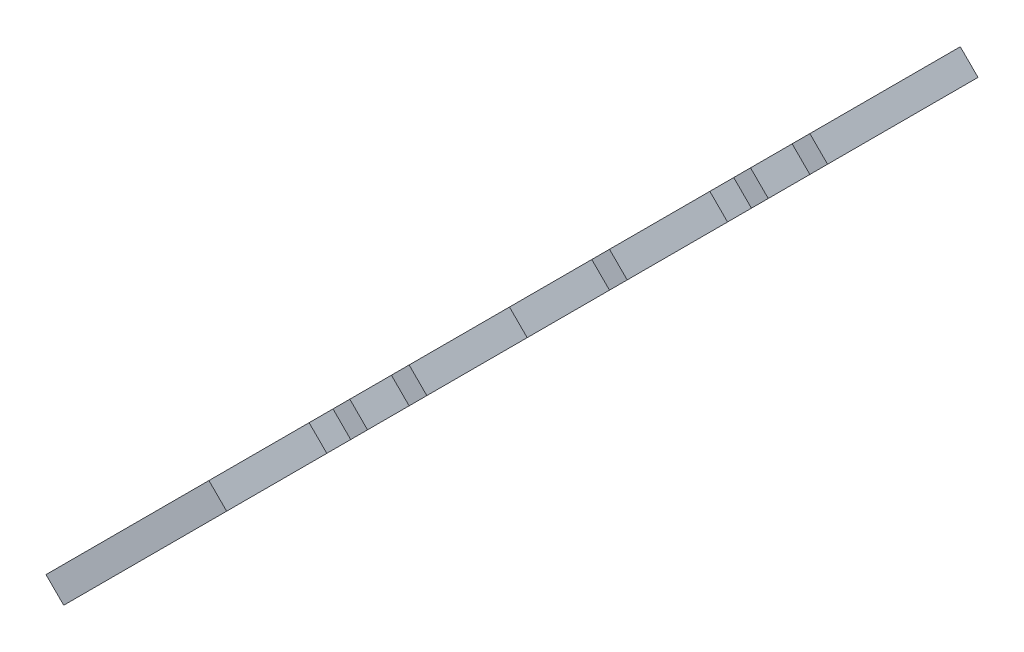
SolidWorks part; units mm, degrees
ref_plane "Front Plane" through (0, 0, 0) normal (0, 0, 1) x (1, 0, 0)
ref_plane "Top Plane" through (0, 0, 0) normal (0, 1, 0) x (1, 0, 0)
ref_plane "Right Plane" through (0, 0, 0) normal (1, 0, 0) x (0, 0, -1)
sketch "Sketch1" plane through (0, 0, 0) normal (0, 0, 1) x (1, 0, 0)
  line L0 (-110.4572, 6.7859) -> (-69.148, 48.095)
  line L1 (-110.4572, 6.7859) -> (-114.9473, 11.276)
  line L2 (-69.148, 48.095) -> (-73.6381, 52.5852)
  line L3 (-114.9473, 11.276) -> (-73.6381, 52.5852)
  line L4 (-74.5361, -29.1352) -> (-70.046, -24.645) construction
extrude "Boss-Extrude1" add sketch "Sketch1" along normal up to surface (190.5 mm away)
sketch "Sketch2" plane through (-63.1116, 63.1116, 0) normal (-0.7071, 0.7071, 0) x (0, 0, 1)
  line L0 (190.5, -14.8867) -> (0, -14.8867) construction
  line L1 (165.1, -21.2367) -> (139.7412, -21.2367)
  line L2 (165.1, -21.2367) -> (165.1, -14.8867)
  line L3 (165.1, -14.8867) -> (139.7412, -14.8867)
  line L4 (139.7412, -21.2367) -> (139.7412, -14.8867)
  line L5 (190.5, -73.3067) -> (0, -73.3067) construction
  line L6 (165.1, -66.9567) -> (139.7412, -66.9567)
  line L7 (165.1, -66.9567) -> (165.1, -73.3067)
  line L8 (165.1, -73.3067) -> (139.7412, -73.3067)
  line L9 (139.7412, -66.9567) -> (139.7412, -73.3067)
  dimension "D1" = 25.3588
extrude "Cut-Extrude1" cut sketch "Sketch2" against normal blind 6.35
pattern_linear "LPattern1" count 3 spacing 50.8 along (0, 0, -1) of "Cut-Extrude1"
sketch "Sketch3" plane through (0, 0, 0) normal (0, 0, -1) x (-1, 0, 0)
  line L0 (94.2927, 22.9503) -> (98.7828, 27.4404)
  line L1 (110.4572, 6.7859) -> (69.148, 48.095) construction
  line L2 (73.6381, 52.5852) -> (114.9473, 11.276) construction
  line L3 (98.7828, 27.4404) -> (89.8026, 36.4207)
  line L4 (89.8026, 36.4207) -> (85.3124, 31.9306)
  line L6 (85.3124, 31.9306) -> (94.2927, 22.9503)
  line L7 (98.7828, 36.4207) -> (83.4753, 21.1131) construction
  line L8 (69.148, 48.095) -> (73.6381, 52.5852) construction
  line L9 (114.9473, 11.276) -> (110.4572, 6.7859) construction
  dimension "D1" = 12.7
  dimension "D2" = 6.35
extrude "Boss-Extrude2" add sketch "Sketch3" along normal blind 6.35
sketch "Sketch5" plane through (-58.6215, 58.6215, 0) normal (0.7071, -0.7071, 0) x (0, 0, -1)
  line L0 (-179.8955, -73.3067) -> (-175.7045, -66.9567) construction
  line L1 (-190.5, -73.3067) -> (-165.1, -73.3067) construction
  line L2 (-179.8955, -66.9567) -> (-179.8955, -73.3067) construction
  line L3 (-175.7045, -73.3067) -> (-179.8955, -66.9567) construction
  line L4 (-175.7045, -66.9567) -> (-175.7045, -73.3067) construction
  line L5 (-78.2955, -73.3067) -> (-74.1045, -66.9567) construction
  line L6 (-88.9412, -73.3067) -> (-63.5, -73.3067) construction
  line L7 (-78.2955, -66.9567) -> (-78.2955, -73.3067) construction
  line L8 (-74.1045, -73.3067) -> (-78.2955, -66.9567) construction
  line L9 (-74.1045, -66.9567) -> (-74.1045, -73.3067) construction
  line L10 (-17.9705, -73.3067) -> (-13.7795, -66.9567) construction
  line L11 (-38.1412, -73.3067) -> (0, -73.3067) construction
  line L12 (-17.9705, -66.9567) -> (-17.9705, -73.3067) construction
  line L13 (-13.7795, -73.3067) -> (-17.9705, -66.9567) construction
  line L14 (-13.7795, -66.9567) -> (-13.7795, -73.3067) construction
  circle A0 centre (-177.8, -70.1317) radius 2.0955
  circle A1 centre (-76.2, -70.1317) radius 2.0955
  circle A2 centre (-15.875, -70.1317) radius 2.0955
  dimension "D1" = 4.191
extrude "Cut-Extrude2" cut sketch "Sketch5" against normal through all
ref_plane "Midplane" through (-31.1811, -31.1811, 0) normal (-0.7071, -0.7071, 0) x (-0.7071, 0.7071, 0)
mirror "Mirror1" about plane through (-31.1811, -31.1811, 0) normal (-0.7071, -0.7071, 0) of "Cut-Extrude2"
sketch "Sketch6" plane through (-63.1116, 63.1116, 0) normal (-0.7071, 0.7071, 0) x (0, 0, 1)
  line L0 (152.4206, -3.6091) -> (152.4206, -40.9822) construction
  line L1 (139.7412, -14.8867) -> (139.7412, -21.2367) construction
  line L2 (165.1, -21.2367) -> (165.1, -14.8867) construction
  line L3 (50.8206, 6.6062) -> (50.8206, -35.0025) construction
  line L4 (38.1412, -14.8867) -> (38.1412, -21.2367) construction
  line L5 (63.5, -21.2367) -> (63.5, -14.8867) construction
  line L7 (38.1412, -21.2367) -> (63.5, -21.2367) construction
  line L11 (139.7412, -21.2367) -> (165.1, -21.2367) construction
  line B0 (52.9542, -21.2367) -> (48.687, -21.2367)
  line B1 (48.687, -33.1747) -> (46.3756, -33.1747)
  line B2 (46.3756, -33.1747) -> (46.3756, -29.9997)
  line B3 (46.3756, -29.9997) -> (48.687, -29.9997)
  line B4 (48.687, -29.9997) -> (48.687, -21.2367)
  line B5 (48.687, -33.1747) -> (48.687, -36.4767)
  line B6 (48.687, -36.4767) -> (52.9542, -36.4767)
  line B7 (52.9542, -33.1747) -> (52.9542, -36.4767)
  line B8 (52.9542, -29.9997) -> (52.9542, -21.2367)
  line B9 (55.2656, -29.9997) -> (52.9542, -29.9997)
  line B10 (55.2656, -33.1747) -> (55.2656, -29.9997)
  line B11 (52.9542, -33.1747) -> (55.2656, -33.1747)
  line B12 (154.5542, -21.2367) -> (150.287, -21.2367)
  line B13 (150.287, -33.1747) -> (147.9756, -33.1747)
  line B14 (147.9756, -33.1747) -> (147.9756, -29.9997)
  line B15 (147.9756, -29.9997) -> (150.287, -29.9997)
  line B16 (150.287, -29.9997) -> (150.287, -21.2367)
  line B17 (150.287, -33.1747) -> (150.287, -36.4767)
  line B18 (150.287, -36.4767) -> (154.5542, -36.4767)
  line B19 (154.5542, -33.1747) -> (154.5542, -36.4767)
  line B20 (154.5542, -29.9997) -> (154.5542, -21.2367)
  line B21 (156.8656, -29.9997) -> (154.5542, -29.9997)
  line B22 (156.8656, -33.1747) -> (156.8656, -29.9997)
  line B23 (154.5542, -33.1747) -> (156.8656, -33.1747)
sketch_block_instance "TSlot-1"
sketch_block "TSlot" parameters "D1"=3.302, "D2"=3.175
sketch_block_instance "TSlot-2"
extrude "Cut-Extrude3" cut sketch "Sketch6" against normal through all
mirror "Mirror2" about plane through (-31.1811, -31.1811, 0) normal (-0.7071, -0.7071, 0) of "Cut-Extrude3"
sketch "Sketch7" plane through (-63.1116, 63.1116, 0) normal (-0.7071, 0.7071, 0) x (0, 0, 1)
  line L0 (0, -26.3167) -> (12.9166, -26.3167) construction
  line L1 (0, -14.8867) -> (0, -37.7467) construction
  line L2 (0, -61.8767) -> (18.0361, -61.8767) construction
  line L3 (0, -50.4467) -> (0, -73.3067) construction
  line B0 (0, -24.1831) -> (0, -28.4503)
  line B1 (11.938, -28.4503) -> (11.938, -30.7617)
  line B2 (11.938, -30.7617) -> (8.763, -30.7617)
  line B3 (8.763, -30.7617) -> (8.763, -28.4503)
  line B4 (8.763, -28.4503) -> (0, -28.4503)
  line B5 (11.938, -28.4503) -> (15.24, -28.4503)
  line B6 (15.24, -28.4503) -> (15.24, -24.1831)
  line B7 (11.938, -24.1831) -> (15.24, -24.1831)
  line B8 (8.763, -24.1831) -> (0, -24.1831)
  line B9 (8.763, -21.8717) -> (8.763, -24.1831)
  line B10 (11.938, -21.8717) -> (8.763, -21.8717)
  line B11 (11.938, -24.1831) -> (11.938, -21.8717)
  line B12 (0, -59.7431) -> (0, -64.0103)
  line B13 (11.938, -64.0103) -> (11.938, -66.3217)
  line B14 (11.938, -66.3217) -> (8.763, -66.3217)
  line B15 (8.763, -66.3217) -> (8.763, -64.0103)
  line B16 (8.763, -64.0103) -> (0, -64.0103)
  line B17 (11.938, -64.0103) -> (15.24, -64.0103)
  line B18 (15.24, -64.0103) -> (15.24, -59.7431)
  line B19 (11.938, -59.7431) -> (15.24, -59.7431)
  line B20 (8.763, -59.7431) -> (0, -59.7431)
  line B21 (8.763, -57.4317) -> (8.763, -59.7431)
  line B22 (11.938, -57.4317) -> (8.763, -57.4317)
  line B23 (11.938, -59.7431) -> (11.938, -57.4317)
sketch_block_instance "TSlot-3"
sketch_block_instance "TSlot-4"
extrude "Cut-Extrude4" cut sketch "Sketch7" against normal through all
